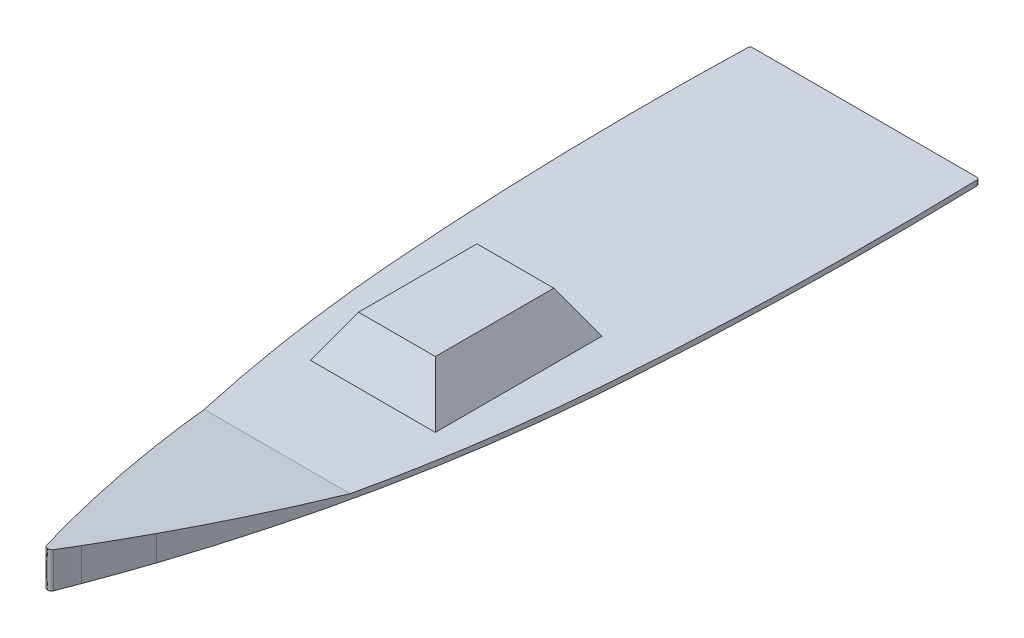
SolidWorks part; units mm, degrees
ref_plane "Front" through (0, 0, 0) normal (0, 0, 1) x (1, 0, 0)
ref_plane "Top" through (0, 0, 0) normal (0, 1, 0) x (1, 0, 0)
ref_plane "Right" through (0, 0, 0) normal (1, 0, 0) x (0, 0, -1)
sketch "Sketch1" plane through (0, 0, 0) normal (0, 1, 0) x (1, 0, 0)
  line L0 (282.1786, 648.2956) -> (-266.7422, 648.2956)
  arc A0 (16.5833, -1339.5499) -> (35.2929, -1290.6614) centre (-3527.9309, 44.9642) ccw
  arc A1 (-19.8565, -1290.6614) -> (-1.1468, -1339.5499) centre (3543.3673, 44.9642) ccw
  spline S0 degree 3 poles (16.5833, -1339.5499) (16.2374, -1340.4352) (15.2788, -1342.1014) (13.1668, -1344.0649) (10.5695, -1345.3177) (8.6687, -1345.6044) (7.7182, -1345.6044) knots 0.80827 0.80827 0.80827 0.80827 0.856202 0.904135 0.952067 1 1 1 1
  spline S1 degree 3 poles (-1.1468, -1339.5499) (-0.801, -1340.4352) (0.1577, -1342.1014) (2.2696, -1344.0649) (4.8669, -1345.3177) (6.7677, -1345.6044) (7.7182, -1345.6044) knots 0.80827 0.80827 0.80827 0.80827 0.856202 0.904135 0.952067 1 1 1 1
  spline S2 degree 3 poles (83.204, -1155.1044) (67.9931, -1200.8755) (52.2219, -1245.4977) (35.2929, -1290.6614) knots 0 0 0 0 1 1 1 1
  spline S3 degree 3 poles (-67.7675, -1155.1044) (-52.5567, -1200.8755) (-36.7855, -1245.4977) (-19.8565, -1290.6614) knots 0 0 0 0 1 1 1 1
  spline S4 degree 3 poles (-271.8271, 643.3635) (-275.6191, 513.3418) (-276.5448, 362.6273) (-273.086, 195.0449) (-271.0316, 119.8478) (-268.6716, 56.063) (-263.1321, -66.0697) (-257.4333, -160.0376) (-250.764, -248.7462) (-248.4873, -276.9856) (-240.1828, -371.0928) (-227.55, -472.7787) (-212.6105, -566.462) (-203.2227, -622.637) (-193.8441, -673.2376) (-182.2907, -729.9376) (-174.2712, -767.8308) (-162.8967, -818.3718) (-149.2527, -874.9597) (-120.2118, -987.7968) (-92.3477, -1081.14) (-67.7675, -1155.1044) knots 0.002731 0.002731 0.002731 0.002731 0.21875 0.253284 0.28125 0.34375 0.359375 0.484375 0.5 0.506596 0.53125 0.65625 0.675583 0.6875 0.75 0.760136 0.78125 0.8125 0.84375 0.875 1 1 1 1
  spline S5 degree 3 poles (287.2635, 643.3635) (291.0555, 513.3418) (291.9813, 362.6273) (288.5224, 195.0449) (286.468, 119.8478) (284.108, 56.063) (278.5685, -66.0697) (272.8698, -160.0376) (266.2005, -248.7462) (263.9237, -276.9856) (255.6192, -371.0928) (242.9864, -472.7787) (228.047, -566.462) (218.6592, -622.637) (209.2806, -673.2376) (197.7272, -729.9376) (189.7077, -767.8308) (178.3332, -818.3718) (164.6891, -874.9597) (135.6483, -987.7968) (107.7842, -1081.14) (83.204, -1155.1044) knots 0.002731 0.002731 0.002731 0.002731 0.21875 0.253284 0.28125 0.34375 0.359375 0.484375 0.5 0.506596 0.53125 0.65625 0.675583 0.6875 0.75 0.760136 0.78125 0.8125 0.84375 0.875 1 1 1 1
  spline S6 degree 3 poles (287.2635, 643.3635) (287.2539, 643.6927) (287.2127, 644.0157) (287.1054, 644.491) (287.062, 644.6479) (286.9597, 644.9586) (286.9003, 645.113) (286.7024, 645.5619) (286.5433, 645.8451) (286.1716, 646.3798) (285.9567, 646.6329) (285.4893, 647.0863) (285.2356, 647.2892) (284.8247, 647.5573) (284.682, 647.6409) (284.3921, 647.7924) (284.2443, 647.8607) (283.4918, 648.1661) (282.8375, 648.2956) (282.1786, 648.2956) knots 0 0 0 0 0.125 0.125 0.1875 0.1875 0.25 0.25 0.375 0.375 0.5 0.5 0.625 0.625 0.6875 0.6875 0.75 0.75 1 1 1 1
  spline S7 degree 3 poles (-266.7422, 648.2956) (-267.0716, 648.2956) (-267.3956, 648.2639) (-267.8739, 648.1709) (-268.0321, 648.1323) (-268.3457, 648.0394) (-268.5018, 647.9848) (-268.9566, 647.8006) (-269.2446, 647.6504) (-269.7905, 647.2955) (-270.0502, 647.0885) (-270.518, 646.6354) (-270.7286, 646.3882) (-271.0093, 645.9859) (-271.0973, 645.8459) (-271.2577, 645.5607) (-271.3306, 645.4151) (-271.5275, 644.9694) (-271.6302, 644.6605) (-271.7761, 644.0183) (-271.8175, 643.6928) (-271.8271, 643.3635) knots 0 0 0 0 0.125 0.125 0.1875 0.1875 0.25 0.25 0.375 0.375 0.5 0.5 0.625 0.625 0.6875 0.6875 0.75 0.75 0.875 0.875 1 1 1 1
extrude "Boss-Extrude1" add sketch "Sketch1" along normal blind 12.7
sketch "Sketch2" plane through (0, 12.7, 0) normal (0, 1, 0) x (1, 0, 0)
  line L0 (7.7182, -1345.6044) -> (7.7182, 648.2956) construction
  line L1 (282.1786, 648.2956) -> (-266.7422, 648.2956) construction
  line L3 (160.1182, -145.4544) -> (-144.6818, -145.4544)
  line L4 (160.1182, -145.4544) -> (160.1182, -551.8544)
  line L5 (160.1182, -551.8544) -> (-144.6818, -551.8544)
  line L6 (-144.6818, -145.4544) -> (-144.6818, -551.8544)
  line L7 (160.1182, -145.4544) -> (-144.6818, -551.8544) construction
  line L8 (160.1182, -551.8544) -> (-144.6818, -145.4544) construction
  point P3 (7.7182, -351.7044)
  point P6 (7.7182, -348.6544)
  dimension "D1" = 1000
  dimension "D2" = 304.8
  dimension "D3" = 406.4
extrude "Boss-Extrude2" add sketch "Sketch2" along normal blind 101.6 draft 30
ref_axis "Axis1" through (7.7182, 12.7, 1345.6044) along (0, 0, -1)
ref_plane "Plane1" through (7.7182, 0, 0) normal (1, 0, 0) x (0, 0, -1)
sketch "Sketch3" plane through (7.7182, 0, 0) normal (1, 0, 0) x (0, 0, -1)
  line L0 (-1345.6044, 83.8169) -> (-1345.6044, 87.698)
  line L1 (-1345.6044, 12.7) -> (-1345.6044, 83.8169)
  line L3 (-1345.6044, 87.698) -> (-785.3395, 12.7)
  line L4 (643.3635, 12.7) -> (-1155.1044, 12.7) construction
sketch "Sketch4" plane through (0, 12.7, 0) normal (0, 1, 0) x (1, 0, 0)
  line L0 (-170.2898, -785.3395) -> (185.7262, -785.3395)
  arc A0 (16.5833, -1339.5499) -> (35.2929, -1290.6614) centre (-3527.9309, 44.9642) ccw construction
  arc A1 (-19.8565, -1290.6614) -> (-1.1468, -1339.5499) centre (3543.3673, 44.9642) ccw construction
  arc A2 (16.5833, -1339.5499) -> (35.2929, -1290.6614) centre (-3527.9309, 44.9642) ccw
  arc A3 (-19.8565, -1290.6614) -> (-1.1468, -1339.5499) centre (3543.3673, 44.9642) ccw
  spline S0 degree 3 poles (297.8739, 3578.0828) (-100.5704, 2428.5871) (-296.3324, 1321.3403) (-273.086, 195.0449) (-271.0316, 119.8478) (-268.6716, 56.063) (-263.1321, -66.0697) (-257.4333, -160.0376) (-250.764, -248.7462) (-248.4873, -276.9856) (-240.1828, -371.0928) (-227.55, -472.7787) (-212.6105, -566.462) (-203.2227, -622.637) (-193.8441, -673.2376) (-182.2907, -729.9376) (-174.2712, -767.8308) (-162.8967, -818.3718) (-149.2527, -874.9597) (139.3622, -1996.3621) (926.8428, -3004.3909) (2021.0927, -3096.7946) knots -1.59063 -1.59063 -1.59063 -1.59063 0.21875 0.253284 0.28125 0.34375 0.359375 0.484375 0.5 0.506596 0.53125 0.65625 0.675583 0.6875 0.75 0.760136 0.78125 0.8125 0.84375 0.875 2.67592 2.67592 2.67592 2.67592 only from (-271.8271, 643.3635) to (-67.7675, -1155.1044) construction
  spline S1 degree 3 poles (-2005.6904, -3096.7974) (-911.4225, -3004.4115) (-123.9286, -1996.3734) (164.6891, -874.9597) (178.3332, -818.3718) (189.7077, -767.8308) (197.7272, -729.9376) (209.2806, -673.2376) (218.6592, -622.637) (228.047, -566.462) (242.9864, -472.7787) (255.6192, -371.0928) (263.9237, -276.9856) (266.2005, -248.7462) (272.8698, -160.0376) (278.5685, -66.0697) (284.108, 56.063) (286.468, 119.8478) (288.5224, 195.0449) (311.7687, 1321.336) (116.0084, 2428.5784) (-282.4327, 3578.0691) knots -1.673207 -1.673207 -1.673207 -1.673207 0.127731 0.158981 0.190231 0.221481 0.242595 0.252731 0.315231 0.327148 0.346481 0.471481 0.496136 0.502731 0.518356 0.643356 0.658981 0.721481 0.749447 0.783981 2.593354 2.593354 2.593354 2.593354 only from (83.204, -1155.1044) to (287.2635, 643.3635) construction
  spline S2 degree 3 poles (2771.4778, -204.7542) (-139.5761, -1128.5763) (-24.7886, -1362.3738) (13.1668, -1344.0649) (44.0303, -1315.3724) (-131.9781, -1123.3893) (-2051.6109, -3498.7793) knots -1.149333 -1.149333 -1.149333 -1.149333 0.856202 0.904135 0.952067 2.957595 2.957595 2.957595 2.957595 only from (7.7182, -1345.6044) to (16.5833, -1339.5499) construction
  spline S3 degree 3 poles (2067.0684, -3498.8053) (147.4158, -1123.388) (-28.594, -1315.3723) (2.2696, -1344.0649) (40.2249, -1362.3737) (155.0118, -1128.578) (-2755.9918, -204.7594) knots -1.149333 -1.149333 -1.149333 -1.149333 0.856202 0.904135 0.952067 2.957595 2.957595 2.957595 2.957595 only from (-1.1468, -1339.5499) to (7.7182, -1345.6044) construction
  spline S4 degree 3 poles (-1205.107, -4022.1233) (540.4516, -123.4746) (-257.2648, -2380.4962) (834.6697, 1749.0968) knots -9.25201 -9.25201 -9.25201 -9.25201 10.251911 10.251911 10.251911 10.251911 only from (35.2929, -1290.6614) to (83.204, -1155.1044) construction
  spline S5 degree 3 poles (-819.2499, 1749.1597) (272.7038, -2380.4982) (-525.0159, -123.4777) (1220.5169, -4022.064) knots -9.25201 -9.25201 -9.25201 -9.25201 10.251911 10.251911 10.251911 10.251911 only from (-67.7675, -1155.1044) to (-19.8565, -1290.6614) construction
  spline S6 degree 3 poles (7.7182, -1345.6044) (8.6687, -1345.6044) (10.5695, -1345.3177) (13.1668, -1344.0649) (15.2788, -1342.1014) (16.2374, -1340.4352) (16.5833, -1339.5499) knots 0.80827 0.80827 0.80827 0.80827 0.856202 0.904135 0.952067 1 1 1 1
  spline S7 degree 3 poles (-1.1468, -1339.5499) (-0.801, -1340.4352) (0.1577, -1342.1014) (2.2696, -1344.0649) (4.8669, -1345.3177) (6.7677, -1345.6044) (7.7182, -1345.6044) knots 0.80827 0.80827 0.80827 0.80827 0.856202 0.904135 0.952067 1 1 1 1
  spline S8 degree 3 poles (35.2929, -1290.6614) (52.2219, -1245.4977) (67.9931, -1200.8755) (83.204, -1155.1044) knots 0 0 0 0 1 1 1 1
  spline S9 degree 3 poles (-67.7675, -1155.1044) (-52.5567, -1200.8755) (-36.7855, -1245.4977) (-19.8565, -1290.6614) knots 0 0 0 0 1 1 1 1
  spline S10 degree 3 poles (83.204, -1155.1044) (107.7842, -1081.14) (135.6483, -987.7968) (164.6891, -874.9597) (176.4356, -826.2417) (183.2622, -796.3531) (185.7262, -785.3395) knots 0.002731 0.002731 0.002731 0.002731 0.127731 0.158981 0.190231 0.208443 0.208443 0.208443 0.208443
  spline S11 degree 3 poles (-170.2898, -785.3395) (-167.8258, -796.3531) (-160.9992, -826.2417) (-149.2527, -874.9597) (-120.2118, -987.7968) (-92.3477, -1081.14) (-67.7675, -1155.1044) knots 0.794288 0.794288 0.794288 0.794288 0.8125 0.84375 0.875 1 1 1 1
ref_plane "tip" through (0, 0, 1345.6044) normal (0, 0, -1) x (0, 1, 0)
sketch "Sketch5" plane through (0, 0, 1345.6044) normal (0, 0, -1) x (0, 1, 0)
  line L0 (83.8169, 7.7182) -> (87.698, 7.7182) construction
  line L1 (83.8169, 1.3682) -> (87.698, 1.3682) construction
  line L2 (83.8169, 1.3682) -> (83.8169, 14.0682)
  line L3 (83.8169, 14.0682) -> (87.698, 14.0682) construction
  line L4 (87.698, 1.3682) -> (87.698, 14.0682)
  line L5 (85.7575, -0.5723) -> (85.7575, 16.0087) construction
  circle A0 centre (85.7575, 7.7182) radius 1.9405 construction
  arc A1 (87.698, 14.0682) -> (83.8169, 14.0682) centre (85.7575, 14.0682) ccw
  arc A2 (87.698, 1.3682) -> (83.8169, 1.3682) centre (85.7575, 1.3682) cw
  dimension "D1" = 12.7
ref_plane "Plane3" through (0, -90.7998, 12.1546) normal (0, 0.9912, -0.1327) x (1, 0, 0)
ref_plane "deck top" through (0, 12.7, 0) normal (0, 1, 0) x (1, 0, 0)
ref_plane "Plane4" through (0, 87.698, 0) normal (0, 1, 0) x (1, 0, 0)
sketch "Sketch6" plane through (0, 87.698, 0) normal (0, 1, 0) x (1, 0, 0)
  line L1 (185.7262, -785.3395) -> (-170.2898, -785.3395)
  line L2 (185.7262, -785.3395) -> (-170.2898, -785.3395)
  arc A2 (16.5833, -1339.5499) -> (35.2929, -1290.6614) centre (-3527.9309, 44.9642) ccw
  arc A3 (-19.8565, -1290.6614) -> (-1.1468, -1339.5499) centre (3543.3673, 44.9642) ccw
  arc A4 (16.5833, -1339.5499) -> (35.2929, -1290.6614) centre (-3527.9309, 44.9642) ccw
  arc A5 (-19.8565, -1290.6614) -> (-1.1468, -1339.5499) centre (3543.3673, 44.9642) ccw
  spline S6 degree 3 poles (-2005.7189, -3096.7998) (-911.4359, -3004.4287) (-123.931, -1996.3828) (164.6891, -874.9597) (336.2679, -163.3455) (303.0802, 547.3636) (281.3694, 2208.6414) knots -1.673223 -1.673223 -1.673223 -1.673223 0.127731 0.158981 0.190231 1.306672 1.306672 1.306672 1.306672 only from (83.204, -1155.1044) to (185.7262, -785.3395)
  spline S7 degree 3 poles (-1205.107, -4022.1233) (540.4516, -123.4746) (-257.2648, -2380.4962) (834.6697, 1749.0968) knots -9.25201 -9.25201 -9.25201 -9.25201 10.251911 10.251911 10.251911 10.251911 only from (35.2929, -1290.6614) to (83.204, -1155.1044)
  spline S8 degree 3 poles (2771.4778, -204.7542) (-139.5761, -1128.5763) (-24.7886, -1362.3738) (13.1668, -1344.0649) (44.0303, -1315.3724) (-131.9781, -1123.3893) (-2051.6109, -3498.7793) knots -1.149333 -1.149333 -1.149333 -1.149333 0.856202 0.904135 0.952067 2.957595 2.957595 2.957595 2.957595 only from (7.7182, -1345.6044) to (16.5833, -1339.5499)
  spline S9 degree 3 poles (2067.0684, -3498.8053) (147.4158, -1123.388) (-28.594, -1315.3723) (2.2696, -1344.0649) (40.2249, -1362.3737) (155.0118, -1128.578) (-2755.9918, -204.7594) knots -1.149333 -1.149333 -1.149333 -1.149333 0.856202 0.904135 0.952067 2.957595 2.957595 2.957595 2.957595 only from (-1.1468, -1339.5499) to (7.7182, -1345.6044)
  spline S10 degree 3 poles (-819.2499, 1749.1597) (272.7038, -2380.4982) (-525.0159, -123.4777) (1220.5169, -4022.064) knots -9.25201 -9.25201 -9.25201 -9.25201 10.251911 10.251911 10.251911 10.251911 only from (-67.7675, -1155.1044) to (-19.8565, -1290.6614)
  spline S11 degree 3 poles (-265.933, 2208.6344) (-287.6439, 547.3617) (-320.8313, -163.3465) (-149.2527, -874.9597) (139.3661, -1996.3773) (926.8646, -3004.4187) (2021.1388, -3096.7985) knots -0.303939 -0.303939 -0.303939 -0.303939 0.8125 0.84375 0.875 2.675945 2.675945 2.675945 2.675945 only from (-170.2898, -785.3395) to (-67.7675, -1155.1044)
  spline S12 degree 3 poles (83.204, -1155.1044) (107.7842, -1081.14) (135.6483, -987.7968) (164.6891, -874.9597) (176.4356, -826.2417) (183.2622, -796.3531) (185.7262, -785.3395) knots 0.002731 0.002731 0.002731 0.002731 0.127731 0.158981 0.190231 0.208443 0.208443 0.208443 0.208443
  spline S13 degree 3 poles (35.2929, -1290.6614) (52.2219, -1245.4977) (67.9931, -1200.8755) (83.204, -1155.1044) knots 0 0 0 0 1 1 1 1
  spline S14 degree 3 poles (7.7182, -1345.6044) (8.6687, -1345.6044) (10.5695, -1345.3177) (13.1668, -1344.0649) (15.2788, -1342.1014) (16.2374, -1340.4352) (16.5833, -1339.5499) knots 0.80827 0.80827 0.80827 0.80827 0.856202 0.904135 0.952067 1 1 1 1
  spline S15 degree 3 poles (-1.1468, -1339.5499) (-0.801, -1340.4352) (0.1577, -1342.1014) (2.2696, -1344.0649) (4.8669, -1345.3177) (6.7677, -1345.6044) (7.7182, -1345.6044) knots 0.80827 0.80827 0.80827 0.80827 0.856202 0.904135 0.952067 1 1 1 1
  spline S16 degree 3 poles (-67.7675, -1155.1044) (-52.5567, -1200.8755) (-36.7855, -1245.4977) (-19.8565, -1290.6614) knots 0 0 0 0 1 1 1 1
  spline S17 degree 3 poles (-170.2898, -785.3395) (-167.8258, -796.3531) (-160.9992, -826.2417) (-149.2527, -874.9597) (-120.2118, -987.7968) (-92.3477, -1081.14) (-67.7675, -1155.1044) knots 0.794288 0.794288 0.794288 0.794288 0.8125 0.84375 0.875 1 1 1 1
  dimension "D1" = 0
extrude "Boss-Extrude3" add sketch "Sketch4" along normal up to vertex (74.998 mm away) up to point (14.0682, 87.698, 1345.6044)
sketch "Sketch7" plane through (0, -90.7998, 12.1546) normal (0, 0.9912, -0.1327) x (1, 0, 0)
  line L0 (-170.2898, -780.0814) -> (185.7262, -780.0814) construction
  line L1 (-170.2898, -780.0814) -> (185.7262, -780.0814) construction
  line L2 (7.7182, -1345.3438) -> (7.7182, -780.0814)
extrude "Cut-Extrude-Thin1" cut sketch "Sketch7" along normal blind 88.9 thin thin type two direction wall 254 second wall 254
